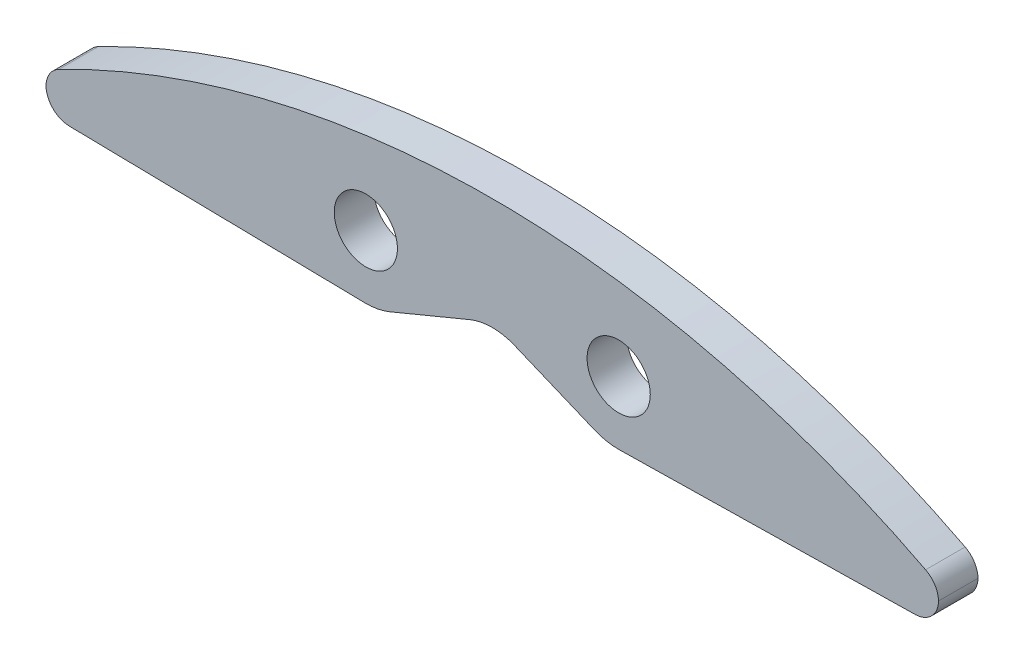
SolidWorks part; units mm, degrees
ref_plane "Front Plane" through (0, 0, 0) normal (0, 0, 1) x (1, 0, 0)
ref_plane "Top Plane" through (0, 0, 0) normal (0, 1, 0) x (1, 0, 0)
ref_plane "Right Plane" through (0, 0, 0) normal (1, 0, 0) x (0, 0, -1)
sketch "Sketch1" plane through (0, 0, 0) normal (0, 0, 1) x (1, 0, 0)
  line L0 (-57.4671, 21.5) -> (58.0784, 21.5) construction
  line L1 (0, 0) -> (0, 18.7938) construction
  line L13 (2.8235, 6.8055) -> (12.9343, 2.6107)
  line L16 (56.4788, 7.378) -> (56.4788, 2.722)
  line L19 (-56.4788, 7.378) -> (-56.4788, 2.722)
  line L22 (16.1429, 2.0013) -> (56.4788, 2.722)
  line L24 (-16.1429, 2.0013) -> (-56.4788, 2.722)
  line L25 (-2.8235, 6.8055) -> (-12.9343, 2.6107)
  circle A2 centre (16, 10) radius 11.5 construction
  arc A11 (-56.4788, 7.378) -> (56.4788, 7.378) centre (0, -98.5) cw
  circle A12 centre (16, 10) radius 4
  circle A13 centre (-16, 10) radius 4
  arc A14 (6.248, 3.905) -> (-2.8235, 6.8055) centre (0, 0) ccw
  circle A15 centre (16, 10) radius 8 construction
  arc A16 (12.9343, 2.6107) -> (16.1429, 2.0013) centre (16, 10) ccw
  arc A17 (-12.9343, 2.6107) -> (-16.1429, 2.0013) centre (-16, 10) cw
  point P7 (50.2525, 2.0013)
  point P21 (0, -12)
  dimension "D1" = 21.5
  dimension "D4" = 8
  dimension "D2" = 120
  dimension "D8" = 16
extrude "Boss-Extrude2" add sketch "Sketch1" along normal blind 5 contours A17 L25 A14 L13 A16 L22 L16 A11 L19 L24 A13 A12 region at (0, 10.5496, 0)
fillet "Fillet3" radius 3 4 edges at (56.4788, 2.722, 2.5) (56.4788, 7.378, 2.5) (-56.4788, 2.722, 2.5) (-56.4788, 7.378, 2.5)
